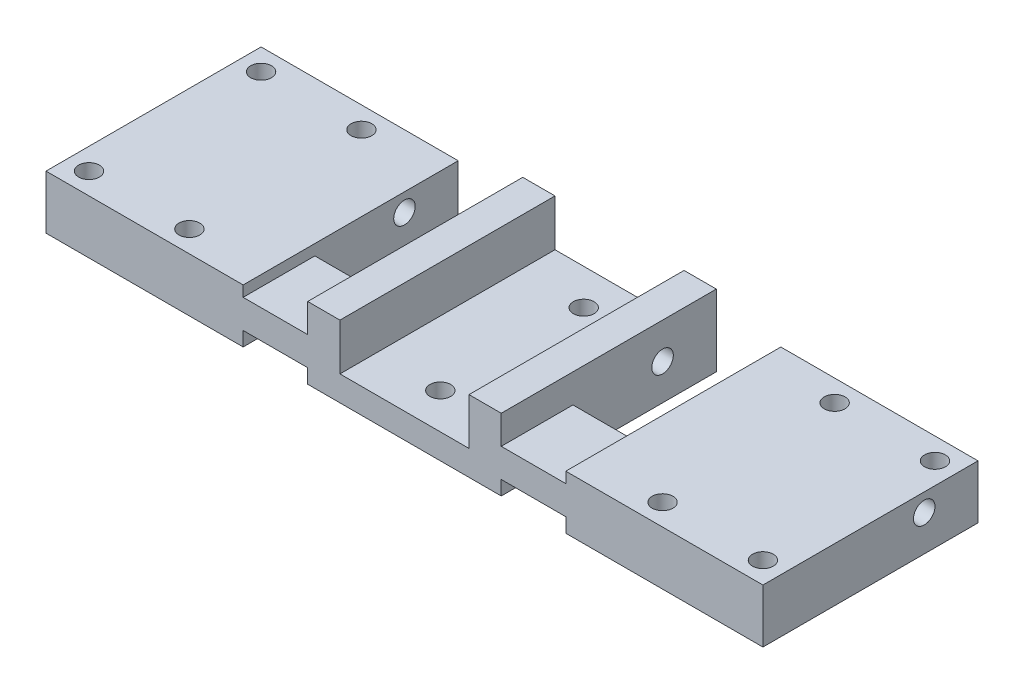
SolidWorks part; units mm, degrees
ref_plane "前视基准面" through (0, 0, 0) normal (0, 0, 1) x (1, 0, 0)
ref_plane "上视基准面" through (0, 0, 0) normal (0, 1, 0) x (1, 0, 0)
ref_plane "右视基准面" through (0, 0, 0) normal (1, 0, 0) x (0, 0, -1)
other "Configuration Table"
sketch "草图1" plane through (0, 0, 0) normal (0, 1, 0) x (1, 0, 0)
  line L0 (-50, 30) -> (-50, 25) construction
  line L1 (0, 0) -> (-100, 0)
  line L2 (0, 0) -> (0, 30)
  line L3 (0, 30) -> (-100, 30)
  line L4 (-100, 0) -> (-100, 30)
  line L5 (-50, 25) -> (-50, 5) construction
  circle A0 centre (-50, 25) radius 1.45
  circle A1 centre (-50, 5) radius 1.45
  dimension "D5" = 2.9
  dimension "D6" = 2.9
  dimension "D1" = 100
  dimension "D2" = 30
  dimension "D3" = 5
  dimension "D4" = 20
extrude "凸台-拉伸1" add sketch "草图1" along normal blind 10
sketch "草图2" plane through (0, 10, 0) normal (0, 1, 0) x (1, 0, 0)
  line L0 (0, 30) -> (-100, 30) construction
  line L1 (-62, 30) -> (-38, 30)
  line L2 (-62, 30) -> (-62, 0)
  line L3 (-62, 0) -> (-38, 0)
  line L4 (-38, 30) -> (-38, 0)
  line L5 (-100, 0) -> (0, 0) construction
  line L6 (-100, 30) -> (-100, 0) construction
  line L7 (0, 0) -> (0, 30) construction
  dimension "D1" = 38
  dimension "D2" = 38
extrude "切除-拉伸1" cut sketch "草图2" against normal blind 6.5
sketch "草图3" plane through (0, 10, 0) normal (0, 1, 0) x (1, 0, 0)
  line L0 (-62, 30) -> (-100, 30) construction
  line L1 (-72.5, 30) -> (-63.5, 30)
  line L2 (-72.5, 30) -> (-72.5, 15)
  line L3 (-72.5, 15) -> (-63.5, 15)
  line L4 (-63.5, 30) -> (-63.5, 15)
  line L5 (-62, 30) -> (-62, 0) construction
  line L6 (-50, 30) -> (-50, 0) construction
  line L7 (-38, 30) -> (-62, 30) construction
  line L8 (-62, 0) -> (-38, 0) construction
  line L9 (-27.5, 15) -> (-36.5, 15)
  line L10 (-36.5, 30) -> (-36.5, 15)
  line L11 (-27.5, 30) -> (-36.5, 30)
  line L12 (-27.5, 30) -> (-27.5, 15)
  dimension "D1" = 15
  dimension "D2" = 9
  dimension "D3" = 1.5
extrude "切除-拉伸2" cut sketch "草图3" against normal blind 16.5
sketch "草图4" plane through (0, 0, -15) normal (0, 0, -1) x (-1, 0, 0)
  line L0 (72.5, 0) -> (72.5, 10) construction
  line L1 (63.5, 10) -> (72.5, 10)
  line L2 (63.5, 10) -> (63.5, 6)
  line L3 (63.5, 6) -> (72.5, 6)
  line L4 (72.5, 10) -> (72.5, 6)
  line L5 (36.5, 10) -> (36.5, 0) construction
  line L6 (27.5, 10) -> (36.5, 10)
  line L7 (27.5, 10) -> (27.5, 6)
  line L8 (27.5, 6) -> (36.5, 6)
  line L9 (36.5, 10) -> (36.5, 6)
  dimension "D1" = 4
  dimension "D2" = 4
extrude "切除-拉伸3" cut sketch "草图4" against normal blind 16.5
sketch "草图6" plane through (-62, 0, 0) normal (1, 0, 0) x (0, 0, -1)
  line L0 (30, 10) -> (22.5, 10) construction
  line L1 (0, 10) -> (30, 10) construction
  line L2 (22.5, 10) -> (22.5, 5) construction
  circle A0 centre (22.5, 5) radius 1.5
  dimension "D3" = 3
  dimension "D1" = 7.5
  dimension "D2" = 5
extrude "切除-拉伸4" cut sketch "草图6" against normal blind 16
sketch "草图7" plane through (-38, 0, 0) normal (-1, 0, 0) x (0, 0, 1)
  circle A0 centre (-22.5, 5) radius 1.5 construction
  circle A1 centre (-22.5, 5) radius 1.5
extrude "切除-拉伸5" cut sketch "草图7" against normal blind 8
chamfer "倒角1" distance 5 angle 45 2 edges at (-68, 6, -15) (-32, 6, -15)
extrude "切除-拉伸8" cut sketch "草图10" against normal blind 30
sketch "草图10" plane through (-100, -149.2845, 244.7238) normal (-1, 0, 0) x (0, 0, 1)
  circle A1 centre (-267.2238, 154.2845) radius 1.5
extrude "切除-拉伸9" cut sketch "草图11" against normal blind 30
sketch "草图11" plane through (0, -149.2845, 244.7238) normal (1, 0, 0) x (0, 0, -1)
  circle A1 centre (267.2238, 154.2845) radius 1.5
sketch "草图15" plane through (0, 0, -30) normal (0, 0, -1) x (-1, 0, 0)
  line L0 (72.5, 10) -> (72.5, 0) construction
  line L1 (0, 10) -> (27.5, 10)
  line L2 (0, 10) -> (0, 7.5)
  line L3 (0, 7.5) -> (27.5, 7.5)
  line L4 (27.5, 10) -> (27.5, 7.5)
  line L5 (100, 10) -> (72.5, 10)
  line L6 (100, 10) -> (100, 7.5)
  line L7 (100, 7.5) -> (72.5, 7.5)
  line L8 (72.5, 10) -> (72.5, 7.5)
  dimension "D1" = 2.5
  dimension "D2" = 2.5
extrude "切除-拉伸14" cut sketch "草图15" against normal up to surface (30 mm away) up to face at (-50, 6.9375, 0)
sketch "草图16" plane through (0, 0, 0) normal (0, 0, 1) x (1, 0, 0)
  line L0 (-100, 0) -> (0, 0) construction
  line L1 (-72.5, 0) -> (-63.5, 0)
  line L2 (-72.5, 0) -> (-72.5, 2)
  line L3 (-72.5, 2) -> (-63.5, 2)
  line L4 (-63.5, 0) -> (-63.5, 2)
  line L6 (-27.5, 0) -> (-36.5, 0)
  line L7 (-27.5, 0) -> (-27.5, 2)
  line L8 (-27.5, 2) -> (-36.5, 2)
  line L9 (-36.5, 0) -> (-36.5, 2)
  dimension "D1" = 2
  dimension "D2" = 2
extrude "切除-拉伸15" cut sketch "草图16" against normal up to next
sketch "草图19" plane through (0, 0, 0) normal (0, -1, 0) x (1, 0, 0)
  line L0 (0, 0) -> (-3, 0) construction
  line L1 (-27.5, 0) -> (0, 0) construction
  line L2 (-3, 0) -> (-3, -3) construction
  line L3 (-3, -3) -> (-17, -3) construction
  line L4 (-17, -3) -> (-17, -27) construction
  line L5 (-17, -27) -> (-3, -27) construction
  line L6 (-50, 0) -> (-50, -13.2237) construction
  line L7 (-63.5, 0) -> (-36.5, 0) construction
  line L8 (-83, -27) -> (-97, -27) construction
  line L9 (-83, -3) -> (-83, -27) construction
  line L10 (-97, -3) -> (-83, -3) construction
  line L11 (-97, 0) -> (-97, -3) construction
  line L12 (-100, 0) -> (-97, 0) construction
  circle A0 centre (-3, -3) radius 1.45
  circle A1 centre (-17, -3) radius 1.45
  circle A2 centre (-17, -27) radius 1.45
  circle A3 centre (-3, -27) radius 1.45
  circle A4 centre (-97, -27) radius 1.45
  circle A5 centre (-83, -27) radius 1.45
  circle A6 centre (-83, -3) radius 1.45
  circle A7 centre (-97, -3) radius 1.45
  dimension "D6" = 2.9
  dimension "D1" = 3
  dimension "D2" = 3
  dimension "D3" = 14
  dimension "D4" = 24
  dimension "D5" = 14
extrude "切除-拉伸18" cut sketch "草图19" against normal through all
sketch "草图21" plane through (-62, 0, 0) normal (1, 0, 0) x (0, 0, -1)
  line L6 (0, 10) -> (30, 10)
  line L7 (0, 10) -> (0, 3.5)
  line L8 (0, 3.5) -> (30, 3.5)
  line L9 (30, 10) -> (30, 3.5)
extrude "凸台-拉伸2" add sketch "草图21" along normal blind 3
sketch "草图22" plane through (-62, 0, 0) normal (-1, 0, 0) x (0, 0, 1)
  circle A1 centre (-22.5, 5) radius 1.5
  circle A2 centre (-22.5, 5) radius 1.5
  dimension "D1" = 0
extrude "切除-拉伸19" cut sketch "草图22" against normal blind 2
sketch "草图23" plane through (-38, 0, 0) normal (-1, 0, 0) x (0, 0, 1)
  line L6 (-30, 10) -> (0, 10)
  line L7 (-30, 10) -> (-30, 3.5)
  line L8 (-30, 3.5) -> (0, 3.5)
  line L9 (0, 10) -> (0, 3.5)
extrude "凸台-拉伸3" add sketch "草图23" along normal blind 3
sketch "草图24" plane through (-38, 0, 0) normal (1, 0, 0) x (0, 0, -1)
  circle A1 centre (22.5, 5) radius 1.5
  circle A2 centre (22.5, 5) radius 1.5
  dimension "D1" = 0
extrude "切除-拉伸20" cut sketch "草图24" against normal blind 2
